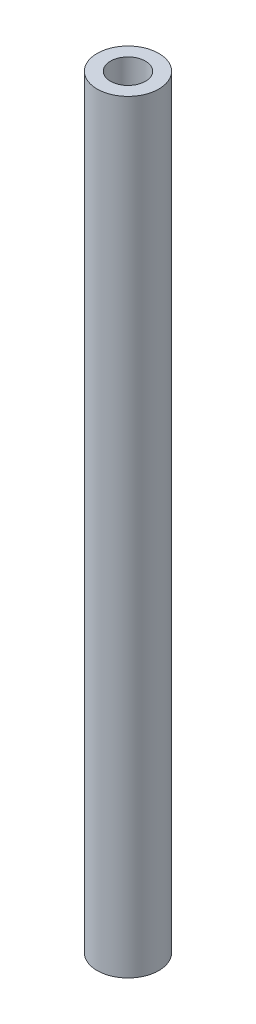
SolidWorks part; units mm, degrees
ref_plane "Front Plane" through (0, 0, 0) normal (0, 0, 1) x (1, 0, 0)
ref_plane "Top Plane" through (0, 0, 0) normal (0, 1, 0) x (1, 0, 0)
ref_plane "Right Plane" through (0, 0, 0) normal (1, 0, 0) x (0, 0, -1)
sketch "Sketch1" plane through (0, 0, 0) normal (0, 1, 0) x (1, 0, 0)
  circle A0 centre (0, 0) radius 2.425
  dimension "D1" = 4.85
extrude "Boss-Extrude1" add sketch "Sketch1" along normal blind 60
sketch "Sketch2" plane through (0, 60, 0) normal (0, 1, 0) x (1, 0, 0)
  circle A0 centre (0, 0) radius 1.375
  dimension "D1" = 2.75
extrude "Cut-Extrude1" cut sketch "Sketch2" against normal blind 11
extrude "Cut-Extrude2" cut sketch "Sketch2<2>" along normal blind 11 from surface starting at face at (0, 0, 2.425)
sketch "Sketch2<2>" plane through (0, 60, 0) normal (0, 1, 0) x (1, 0, 0) same geometry as "Sketch2"
